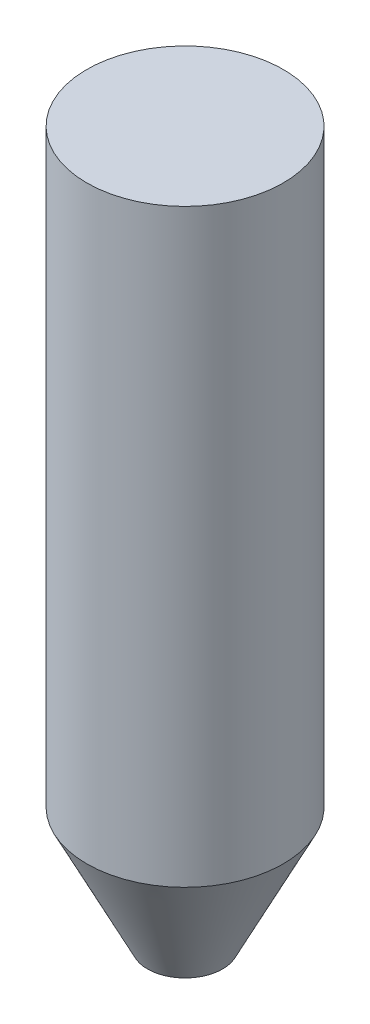
SolidWorks part; units mm, degrees
ref_plane "Front" through (0, 0, 0) normal (0, 0, 1) x (1, 0, 0)
ref_plane "Top" through (0, 0, 0) normal (0, 1, 0) x (1, 0, 0)
ref_plane "Right" through (0, 0, 0) normal (1, 0, 0) x (0, 0, -1)
ref_axis "Center Axis" through (0, 0, -88.99) along (0, 0, 1)
sketch "Sketch1" plane through (0, 0, 0) normal (0, 0, 1) x (1, 0, 0)
  line L0 (0, 32.6644) -> (0, 0) construction
  line L1 (0, 26.0658) -> (19.05, 26.0658)
  line L2 (19.05, 26.0658) -> (0, -12.0342)
  line L3 (0, -12.0342) -> (0, 26.0658)
  point P5 (0, 0)
  dimension "D1" = 38.1
  dimension "D2" = 19.05
revolve "Revolve1" add sketch "Sketch1" angle 360 about L0
sketch "Sketch2" plane through (0, 26.0658, 0) normal (0, 1, 0) x (1, 0, 0)
  circle A0 centre (0, 0) radius 19.05 construction
  circle A1 centre (0, 0) radius 19.05
extrude "Boss-Extrude1" add sketch "Sketch2" along normal blind 114.3
sketch "Sketch4" plane through (0, 0, 0) normal (0, 0, 1) x (1, 0, 0)
  line L0 (-7.2788, 2.5234) -> (7.2788, 2.5234)
  line L1 (-19.05, 26.0658) -> (0, -12.0342) construction
  line L2 (0, -12.0342) -> (19.05, 26.0658) construction
  line L3 (7.2788, 2.5234) -> (0, -12.0342)
  line L4 (0, -12.0342) -> (-7.2788, 2.5234)
  point P6 (0, 0)
extrude "Cut-Extrude5" cut sketch "Sketch4" against normal through all both and the other way through all
